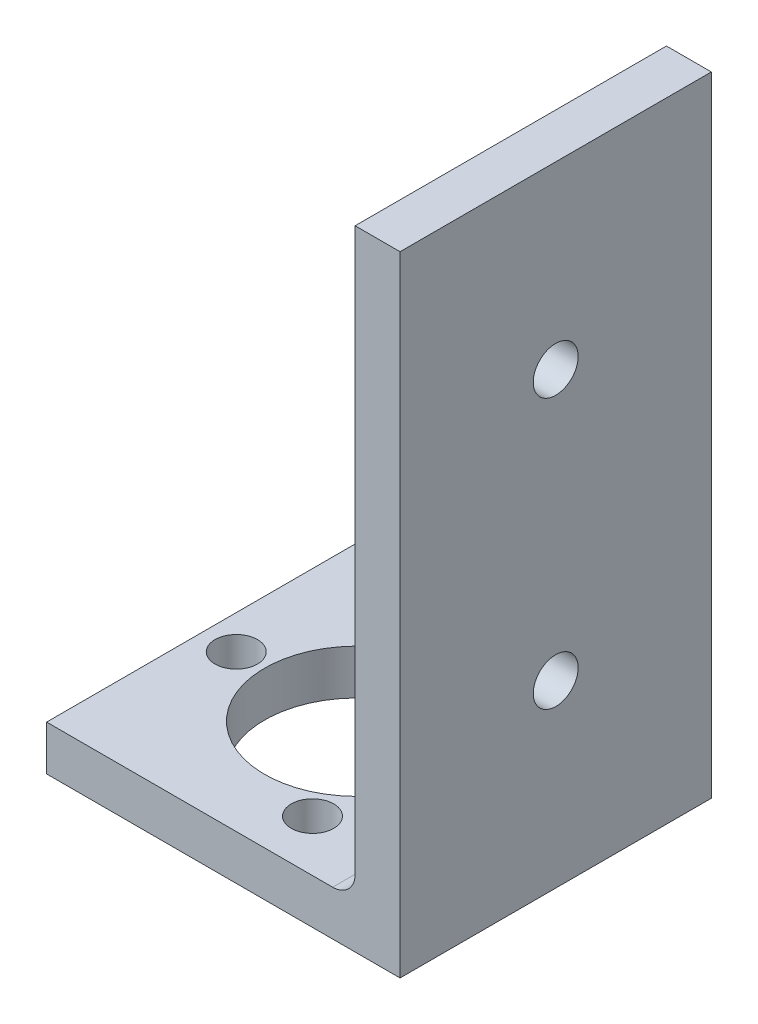
SolidWorks part; units mm, degrees
material "McMaster 6061-T6"
ref_plane "Front Plane" through (0, 0, 0) normal (0, 0, 1) x (1, 0, 0)
ref_plane "Top Plane" through (0, 0, 0) normal (0, 1, 0) x (1, 0, 0)
ref_plane "Right Plane" through (0, 0, 0) normal (1, 0, 0) x (0, 0, -1)
sketch "Sketch2" plane through (0, 0, 0) normal (0, 0, 1) x (1, 0, 0)
  line L0 (-25.4, 0) -> (25.4, 0)
  line L1 (25.4, 0) -> (25.4, 50.8)
  line L2 (25.4, 50.8) -> (22.225, 50.8)
  line L3 (22.225, 50.8) -> (22.225, 3.175)
  line L4 (22.225, 3.175) -> (-25.4, 3.175)
  line L5 (-25.4, 0) -> (-25.4, 3.175)
  line L6 (23.8125, 50.8) -> (25.4, 50.8) construction
  line L7 (-25.4, 1.5875) -> (-25.4, 0) construction
  dimension "Vert" = 50.8
  dimension "Horz" = 50.8
  dimension "Thickness" = 3.175
extrude "Boss-Extrude1" add sketch "Sketch2" along normal mid plane 22
fillet "Fillet1" radius 1.5875 1 edges at (22.225, 3.175, 0)
ref_plane "Contact Plane 1" through (0, 0, 0) normal (0, -1, 0) x (-1, 0, 0)
ref_plane "Contact Plane 2" through (25.4, 0, 0) normal (1, 0, 0) x (0, 0, -1)
ref_plane "Contact Plane 3" through (0, 3.175, 0) normal (0, 1, 0) x (1, 0, 0)
ref_plane "Contact Plane 4" through (22.225, 0, 0) normal (-1, 0, 0) x (0, 0, 1)
ref_plane "Contact Plane 5" through (0, 0, 11) normal (0, 0, 1) x (1, 0, 0)
ref_plane "Contact Plane 6" through (0, 0, -13.54) normal (0, 0, -1) x (-1, 0, 0)
sketch "Sketch3" plane through (0, 0, 11) normal (0, 0, 1) x (1, 0, 0)
  line L0 (-25.4, 0) -> (25.4, 0) construction
  line L1 (6.0591, 71.0024) -> (30.483, 71.0024)
  line L2 (6.0591, 71.0024) -> (6.0591, 44.45)
  line L3 (6.0591, 44.45) -> (30.483, 44.45)
  line L4 (30.483, 71.0024) -> (30.483, 44.45)
  dimension "D1" = 44.45
extrude "Cut-Extrude1" cut sketch "Sketch3" against normal through all
sketch "Sketch4" plane through (0, 0, 0) normal (0, -1, 0) x (1, 0, 0)
  line L0 (15.575, 7.3612) -> (15.575, -7.3612) construction
  line L1 (25.4, 11) -> (25.4, -11) construction
  line L2 (0.425, 11) -> (0.425, -11)
  line L3 (-25.4, 11) -> (25.4, 11) construction
  line L4 (-25.4, -11) -> (25.4, -11) construction
  circle A0 centre (11.325, 0) radius 6.5
  point P4 (15.575, 0)
  point P5 (25.4, 0)
  point P18 (11.325, 0)
  arc B0 (0.425, 0) -> (22.225, 0) centre (11.325, 0) ccw
  arc B1 (22.225, 0) -> (0.425, 0) centre (11.325, 0) ccw
  arc B2 (16.325, 8.6603) -> (14.825, 6.0622) centre (15.575, 7.3612) ccw
  arc B3 (14.825, 6.0622) -> (16.325, 8.6603) centre (15.575, 7.3612) ccw
  arc B4 (4.325, 0) -> (1.325, 0) centre (2.825, 0) ccw
  arc B5 (1.325, 0) -> (4.325, 0) centre (2.825, 0) ccw
  arc B6 (14.825, -6.0622) -> (16.325, -8.6603) centre (15.575, -7.3612) ccw
  arc B7 (16.325, -8.6603) -> (14.825, -6.0622) centre (15.575, -7.3612) ccw
  line M3 (-25.4, -11) -> (25.4, -11)
  line M5 (25.4, 11) -> (-25.4, 11)
  line M6 (-25.4, 11) -> (-25.4, -11)
  dimension "D1" = 13
sketch_block_instance "Block-MotorMounting-1"
sketch_block "Block-MotorMounting"
extrude "Cut-Extrude2" cut sketch "Sketch4" against normal through all contours L2 M5 M6 M3 | B4 B5 | B2 B3 | B6 B7 | L0 A0 | A0 L0 region at (16.9829, 0, -6.984) region at (16.4898, 0, 0) region at (10.6494, 0, 0) region at (15.1978, 0, 5.9533) region at (-12.4875, 0, 0) region at (2.825, 0, 0)
sketch "Sketch5" plane through (25.4, 0, 0) normal (1, 0, 0) x (0, 0, -1)
  line L0 (0, 44.45) -> (0, 31.75) construction
  line L1 (11, 44.45) -> (-11, 44.45) construction
  line L2 (0, 31.75) -> (0, 12.7) construction
  line L3 (0, 12.7) -> (0, 0) construction
  line L4 (-11, 0) -> (11, 0) construction
  circle A1 centre (0, 31.75) radius 1.5875
  circle A2 centre (0, 12.7) radius 1.5875
  dimension "D1" = 3.175
  dimension "D2" = 12.7
extrude "Cut-Extrude3" cut sketch "Sketch5" against normal through all
equation "\"D1@Fillet1\"=\"Thickness@Sketch2\"/2"
